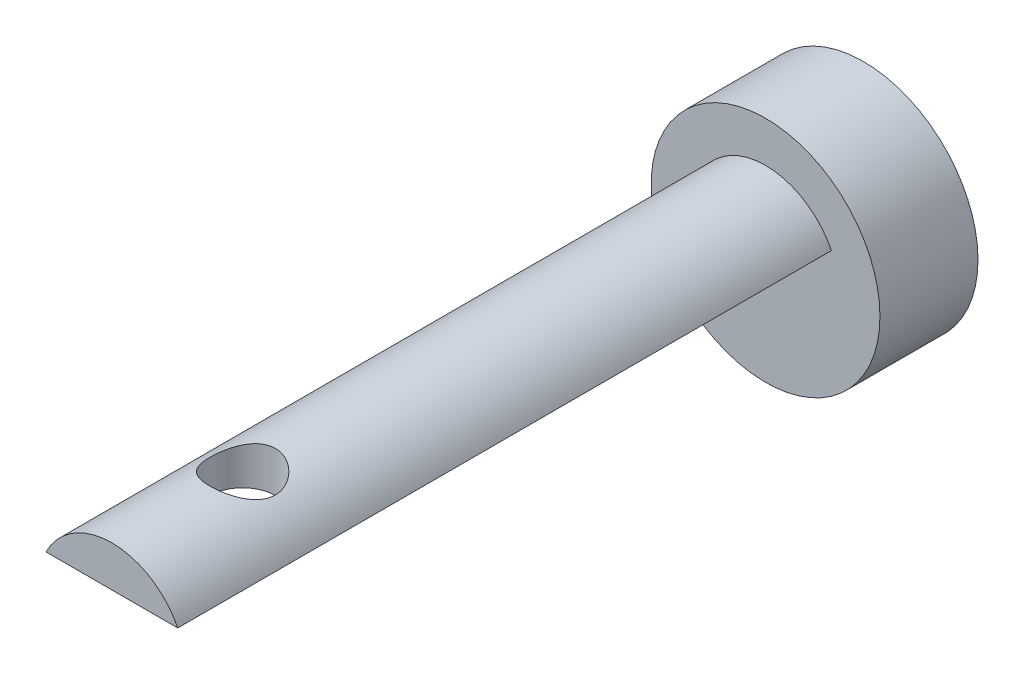
SolidWorks part; units mm, degrees
ref_plane "Front Plane" through (0, 0, 0) normal (0, 0, 1) x (1, 0, 0)
ref_plane "Top Plane" through (0, 0, 0) normal (0, 1, 0) x (1, 0, 0)
ref_plane "Right Plane" through (0, 0, 0) normal (1, 0, 0) x (0, 0, -1)
sketch "Sketch1" plane through (0, 0, 0) normal (0, 0, 1) x (1, 0, 0)
  line L0 (-3.4737, 1) -> (4.1684, 1)
  circle A0 centre (0, 0) radius 3.5
  dimension "D2" = 7
  dimension "D1" = 1
extrude "Boss-Extrude1" add sketch "Sketch1" along normal blind 3 contours L0 A0 | A0 region at (0, 2.0388, 0)
sketch "Sketch2" plane through (0, 0, 3) normal (0, 0, 1) x (1, 0, 0)
  line L0 (-2.0156, 1) -> (2.0156, 1)
  circle A0 centre (0, 0) radius 2.25
  dimension "D1" = 4.5
  dimension "D2" = 1
extrude "Boss-Extrude2" add sketch "Sketch2" along normal blind 20 contours A0 region at (0, 1.5142, 3)
sketch "Sketch3" plane through (0, 1, 0) normal (0, -1, 0) x (-1, 0, 0)
  line L0 (2.0156, -23) -> (-2.0156, -23) construction
  line L1 (2.0156, -3) -> (-2.0156, -3) construction
  circle A0 centre (0, -19) radius 1
  point P4 (0, -23)
  dimension "D1" = 16
  dimension "D2" = 0
  dimension "D3" = 2
extrude "Cut-Extrude1" cut sketch "Sketch3" against normal blind 10
